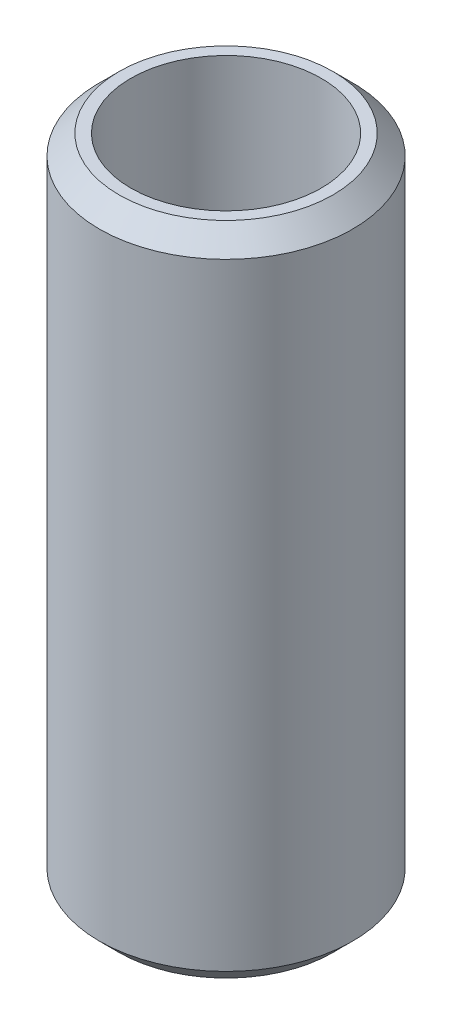
SolidWorks part; units mm, degrees
ref_plane "Front Plane" through (0, 0, 0) normal (0, 0, 1) x (1, 0, 0)
ref_plane "Top Plane" through (0, 0, 0) normal (0, 1, 0) x (1, 0, 0)
ref_plane "Right Plane" through (0, 0, 0) normal (1, 0, 0) x (0, 0, -1)
sketch "Sketch1" plane through (0, 0, 0) normal (0, 1, 0) x (1, 0, 0)
  circle A0 centre (0, 0) radius 37.5
  dimension "SHAFT_OD" = 75
extrude "Boss-Extrude1" add sketch "Sketch1" along normal blind 194.2504
sketch "Sketch2" plane through (0, 0, 0) normal (0, 1, 0) x (1, 0, 0)
  circle A0 centre (0, 0) radius 28.1871
  dimension "BORE_D" = 56.3743
extrude "Cut-Extrude1" cut sketch "Sketch2" along normal through all
chamfer "Chamfer1" distance 5.8398 angle 45 2 edges at (0, 194.2504, 37.5) (0, 0, 37.5)
